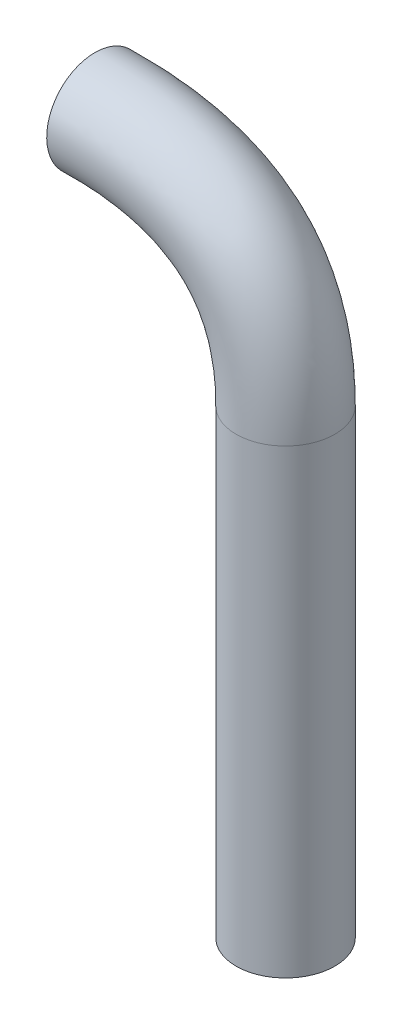
SolidWorks part; units mm, degrees
ref_plane "Front Plane" through (0, 0, 0) normal (0, 0, 1) x (1, 0, 0)
ref_plane "Top Plane" through (0, 0, 0) normal (0, 1, 0) x (1, 0, 0)
ref_plane "Right Plane" through (0, 0, 0) normal (1, 0, 0) x (0, 0, -1)
sketch "Sketch1" plane through (0, 0, 0) normal (0, 1, 0) x (1, 0, 0)
  circle A0 centre (0, 0) radius 7.5
extrude "Boss-Extrude1" add sketch "Sketch1" along normal blind 70
sketch "Sketch3" plane through (0, 70, 0) normal (0, 1, 0) x (1, 0, 0)
  circle A0 centre (0, 0) radius 7.5
sketch "Sketch14" plane through (0, 0, 0) normal (0, 0, 1) x (1, 0, 0)
  line L0 (7.5, 70) -> (-7.5, 70) construction
  spline S0 degree 2 poles (0, 70) (0.0595, 95.1421) (-28.7831, 94.5044) knots 0 0 0 1 1 1
  point P2 (-2.212, 80.8404)
  point P4 (-17.649, 85.4527)
  point P5 (-23.5263, 88.2358)
  point P8 (-20.336, 83.8004)
  point P9 (-3.3726, 81.8551)
  point P10 (-20.4138, 88.4693)
  point P11 (-33.9534, 90.0255)
  point P12 (-3.8394, 84.9676)
  point P13 (-29.0477, 95.4127)
  point P14 (-29.5855, 94.0681)
  point P15 (-28.7579, 94.8372)
  point P16 (-28.7831, 94.5044)
sweep "Sweep4" add profiles "Sketch3" path "Sketch14"
sketch "Sketch15" plane through (0, 0, 0) normal (0, -1, 0) x (1, 0, 0)
  circle A0 centre (0, 0) radius 2
extrude "Cut-Extrude1" cut sketch "Sketch15" against normal blind 10
